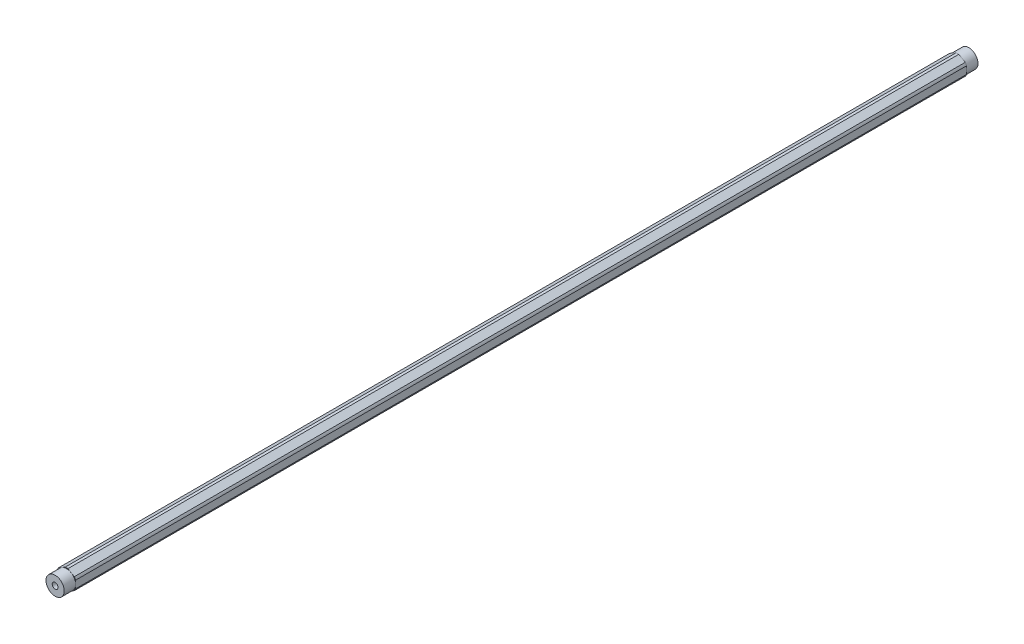
SolidWorks part; units mm, degrees
material "7075-T6 (SN)"
ref_plane "Front Plane" through (0, 0, 0) normal (0, 0, 1) x (1, 0, 0)
ref_plane "Top Plane" through (0, 0, 0) normal (0, 1, 0) x (1, 0, 0)
ref_plane "Right Plane" through (0, 0, 0) normal (1, 0, 0) x (0, 0, -1)
sketch "Sketch2" plane through (0, 0, 0) normal (0, 0, 1) x (1, 0, 0)
  line L1 (0, 7.3323) -> (-6.35, 3.6662)
  line L2 (-6.35, 3.6662) -> (-6.35, -3.6662)
  line L3 (-6.35, -3.6662) -> (0, -7.3323)
  line L4 (0, -7.3323) -> (6.35, -3.6662)
  line L5 (6.35, -3.6662) -> (6.35, 3.6662)
  line L6 (6.35, 3.6662) -> (0, 7.3323)
  circle A0 centre (0, 0) radius 6.35 construction
  circle A2 centre (0, 0) radius 2.0193
  circle A3 centre (0, 0) radius 6.858
  dimension "D1" = 12.7
  dimension "D2" = 13.716
  dimension "D3" = 4.0386
extrude "Boss-Extrude1" add sketch "Sketch2" along normal mid plane 619.125 contours L5 A3 L6 L1 L2 L3 L4 A2 region at (0, 6.6711, 0)
sketch "Sketch7" plane through (0, 0, 309.5625) normal (0, 0, 1) x (1, 0, 0)
  circle A0 centre (0, 0) radius 6.35
  dimension "D1" = 12.7
extrude "Boss-Extrude2" add sketch "Sketch7" along normal blind 7.9375
mirror "Mirror1" about plane through (0, 0, 0) normal (0, 0, 1) of "Boss-Extrude2"
hole_wizard "#10-32 Tapped Hole2" positions "3DSketch1" profile "Sketch6" tap size "#10-32" standard "ANSI Inch"
sketch3d "3DSketch1"
  line L0 (0, 0, 317.5) -> (0, 0, 309.5625) construction
  line L1 (0, 0, -317.5) -> (0, 0, -309.5625) construction
  point P14 (0, 0, 317.5)
  point P18 (0, 0, -317.5)
sketch "Sketch6" plane through (0, 0, 317.5) normal (1, 0, 0) x (0, -1, 0)
  line L0 (0, 0) -> (0, 17.5608)
  line L1 (0, 17.5608) -> (2.0193, 16.3474)
  line L2 (2.0193, 16.3474) -> (2.0193, 0)
  line L5 (2.0193, 0) -> (0, 0)
  line L10 (0, 17.5608) -> (-2.0193, 16.3474) construction
  line L11 (0, -6.35) -> (0, 107.95) construction
  dimension "Tap Drill Dia." = 4.0386
  dimension "Tap Drill Depth" = 16.3474
  dimension "Drill Angle" = 118
cosmetic thread "Hole Thread1" parameters "D1"=13.97, "D2"=4.826
cosmetic thread "Hole Thread2" parameters "D1"=13.97, "D2"=4.826
